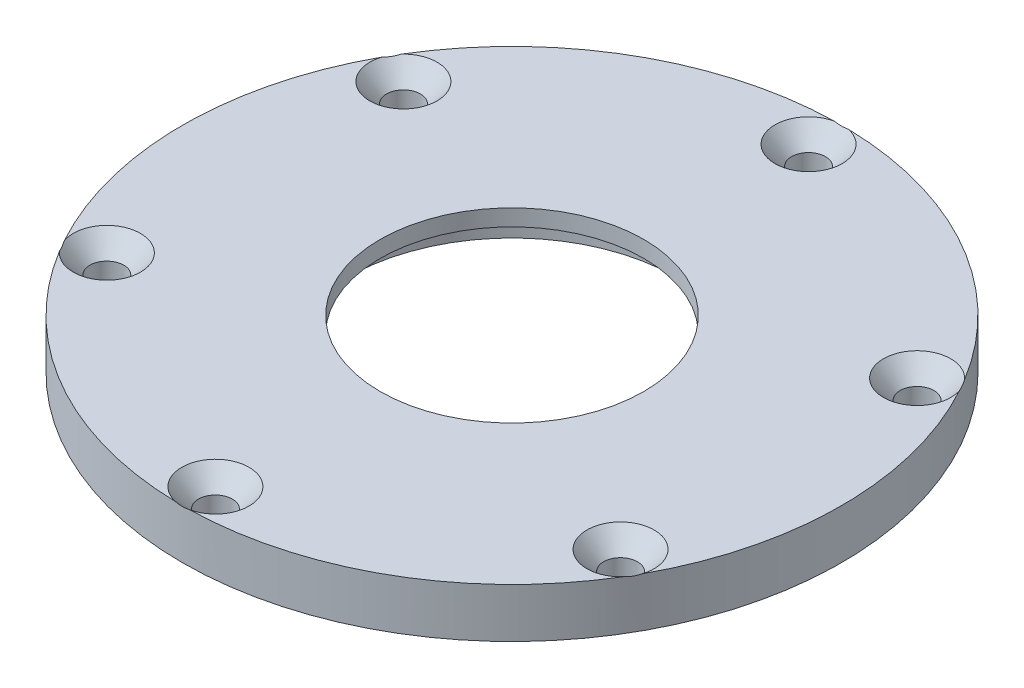
SolidWorks part; units mm, degrees
material "6061-T6 (SS)"
ref_plane "Front Plane" through (0, 0, 0) normal (0, 0, 1) x (1, 0, 0)
ref_plane "Top Plane" through (0, 0, 0) normal (0, 1, 0) x (1, 0, 0)
ref_plane "Right Plane" through (0, 0, 0) normal (1, 0, 0) x (0, 0, -1)
sketch "Sketch1" plane through (0, 0, 0) normal (0, 1, 0) x (1, 0, 0)
  circle A0 centre (0, 0) radius 31.75
  dimension "D1" = 63.5
extrude "Boss-Extrude1" add sketch "Sketch1" along normal blind 4.7625
hole_wizard "CSK for #4 Flat Head Socket Cap Screw1" positions "Sketch5" profile "Sketch4" countersink size "#4" standard "Ansi Inch" end condition through all
sketch "Sketch5" plane through (0, 4.7625, 0) normal (0, 1, 0) x (-1, 0, 0)
  point P0 (0, 28.575)
  point P24 (24.7467, 14.2875)
  point P25 (24.7467, -14.2875)
  point P26 (0, -28.575)
  point P27 (-24.7467, -14.2875)
  point P28 (-24.7467, 14.2875)
  dimension "D1" = 28.575
  dimension "D2" = 6
sketch "Sketch4" plane through (0, 4.7625, 28.575) normal (1, 0, 0) x (0, 0, 1)
  line L0 (0, 0) -> (0, 4.7625)
  line L1 (0, 4.7625) -> (1.6319, 4.7625)
  line L2 (1.6319, 4.7625) -> (1.6319, 1.8481)
  line L3 (1.6319, 1.8481) -> (3.2385, 0)
  line L5 (3.2385, 0) -> (0, 0)
  line L6 (-1.6319, 1.8481) -> (-3.2385, 0) construction
  line L11 (0, -6.35) -> (0, 107.95) construction
  dimension "Thru Hole Dia." = 3.2639
  dimension "Thru Hole Depth" = 4.7625
  dimension "Near C'Sink Dia." = 6.477
  dimension "Near C'Sink Angle" = 82
sketch "Sketch6" plane through (0, 0, 0) normal (0, -1, 0) x (1, 0, 0)
  circle A0 centre (0, 0) radius 15.875
  dimension "D1" = 31.75
extrude "Cut-Extrude1" cut sketch "Sketch6" against normal blind 3.175
sketch "Sketch7" plane through (0, 3.175, 0) normal (0, -1, 0) x (1, 0, 0)
  circle A0 centre (0, 0) radius 12.7
  dimension "D1" = 25.4
extrude "Cut-Extrude2" cut sketch "Sketch7" against normal blind 3.175
sketch "Sketch8" plane through (0, 0, 0) normal (0, -1, 0) x (1, 0, 0)
  arc A0 (-3.167, 28.3494) -> (3.167, 28.3494) centre (0, 28.575) ccw
  circle A1 centre (0, 0) radius 31.75 construction
  arc A2 (22.9678, 16.9174) -> (26.1348, 11.432) centre (24.7467, 14.2875) ccw
  arc A3 (24.649, 17.461) -> (27.4462, 12.6162) centre (24.7467, 14.2875) ccw
  arc A4 (26.1348, -11.432) -> (22.9678, -16.9174) centre (24.7467, -14.2875) ccw
  arc A5 (3.167, -28.3494) -> (-3.167, -28.3494) centre (0, -28.575) ccw
  circle A6 centre (0, 0) radius 17.4625
  arc A7 (-4.9984, 29.7905) -> (-23.3002, 19.224) centre (0, 0) ccw
  arc A8 (-22.9678, -16.9174) -> (-26.1348, -11.432) centre (-24.7467, -14.2875) ccw
  arc A9 (-26.1348, 11.432) -> (-22.9678, 16.9174) centre (-24.7467, 14.2875) ccw
  circle A10 centre (24.7467, -14.2875) radius 3.175 [skipped]
  circle A11 centre (0, -28.575) radius 3.175 [skipped]
  circle A12 centre (-24.7467, -14.2875) radius 3.175 [skipped]
  circle A13 centre (-24.7467, 14.2875) radius 3.175 [skipped]
  circle A14 centre (0, 28.575) radius 1.632 construction
  arc A15 (23.3002, 19.224) -> (4.9984, 29.7905) centre (0, 0) ccw
  arc A16 (-28.2985, 10.5665) -> (-28.2985, -10.5665) centre (0, 0) ccw
  arc A17 (-23.3002, -19.224) -> (-4.9984, -29.7905) centre (0, 0) ccw
  arc A18 (4.9984, -29.7905) -> (23.3002, -19.224) centre (0, 0) ccw
  arc A19 (28.2985, -10.5665) -> (28.2985, 10.5665) centre (0, 0) ccw
  arc A20 (-3.167, -28.3494) -> (-4.9984, -29.7905) centre (-4.7378, -28.2374) cw
  arc A21 (-26.1348, -11.432) -> (-28.2985, -10.5665) centre (-26.8232, -10.0157) cw
  arc A22 (-22.9678, -16.9174) -> (-23.3002, -19.224) centre (-22.0855, -18.2218) ccw
  arc A23 (22.9678, -16.9174) -> (23.3002, -19.224) centre (22.0855, -18.2218) cw
  arc A24 (26.1348, -11.432) -> (28.2985, -10.5665) centre (26.8232, -10.0157) ccw
  arc A25 (-26.1348, 11.432) -> (-28.2985, 10.5665) centre (-26.8232, 10.0157) ccw
  arc A26 (-22.9678, 16.9174) -> (-23.3002, 19.224) centre (-22.0855, 18.2218) cw
  arc A27 (3.167, 28.3494) -> (4.9984, 29.7905) centre (4.7378, 28.2374) cw
  arc A28 (-3.167, 28.3494) -> (-4.9984, 29.7905) centre (-4.7378, 28.2374) ccw
  arc A29 (3.167, -28.3494) -> (4.9984, -29.7905) centre (4.7378, -28.2374) ccw
  arc A30 (22.9678, 16.9174) -> (23.3002, 19.224) centre (22.0855, 18.2218) ccw
  arc A31 (26.1348, 11.432) -> (28.2985, 10.5665) centre (26.8232, 10.0157) cw
  point P43 (-2.7972, -30.0772)
  point P46 (-27.4462, -12.6162)
  point P49 (-24.649, -17.461)
  point P52 (24.649, -17.461)
  point P55 (27.4462, -12.6162)
  point P58 (-27.4462, 12.6162)
  point P67 (2.7972, -30.0772)
  dimension "D1" = 34.925
  dimension "D2" = 1.5748
  dimension "D4" = 1.5748
  dimension "D5" = 1.5748
  dimension "D3" = 6
extrude "Cut-Extrude3" cut sketch "Sketch8" against normal blind 3.175 contours A31 A2 A30 A15 A27 A0 A28 A7 A26 A9 A25 A16 A21 A8 A22 A17 A20 A5 A29 A18 A23 A4 A24 A19 A6 region at (0, 0, 24.5512)
